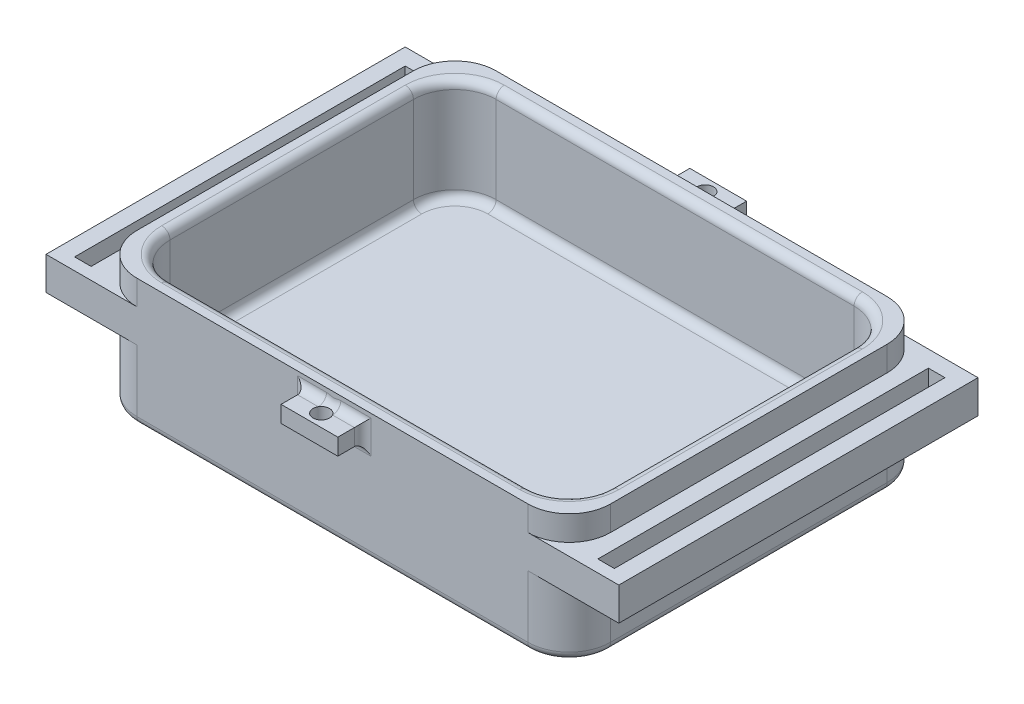
SolidWorks part; units mm, degrees
ref_plane "Front Plane" through (0, 0, 0) normal (0, 0, 1) x (1, 0, 0)
ref_plane "Top Plane" through (0, 0, 0) normal (0, 1, 0) x (1, 0, 0)
ref_plane "Right Plane" through (0, 0, 0) normal (1, 0, 0) x (0, 0, -1)
sketch "Sketch1" plane through (0, 0, 0) normal (0, 1, 0) x (1, 0, 0)
  line L1 (-20.155, 15.23) -> (20.155, 15.23)
  line L2 (-20.155, 15.23) -> (-20.155, -15.23)
  line L3 (-20.155, -15.23) -> (20.155, -15.23)
  line L4 (20.155, 15.23) -> (20.155, -15.23)
  line L5 (-26.155, 4.24) -> (-20.155, 4.24)
  line L6 (-26.155, 4.24) -> (-26.155, -11.5)
  line L7 (-26.155, -11.5) -> (-20.155, -11.5)
  line L8 (-20.155, 4.24) -> (-20.155, -11.5)
  circle A0 centre (17.845, 12.5) radius 1
  circle A1 centre (17.845, -11.5) radius 1
  circle A2 centre (-18.155, -11.5) radius 1
  dimension "D5" = 2
  dimension "D8" = 3.73
  dimension "D10" = 2
  dimension "D11" = 3.73
  dimension "D13" = 2
  dimension "D1" = 40.31
  dimension "D2" = 30.46
  dimension "D3" = 15.23
  dimension "D4" = 20.155
  dimension "D6" = 2.73
  dimension "D7" = 2.31
  dimension "D9" = 2.31
  dimension "D12" = 2
  dimension "D14" = 15.74
  dimension "D15" = 6
  dimension "D16" = 8
  dimension "D17" = 0
sketch "Sketch2" plane through (0, 0, 0) normal (0, 1, 0) x (1, 0, 0)
  line L0 (-20.155, 15.23) -> (20.155, 15.23) construction
  line L1 (-29.655, 18.23) -> (23.655, 18.23)
  line L2 (-29.655, 18.23) -> (-29.655, -21.23)
  line L3 (-29.655, -21.23) -> (23.655, -21.23)
  line L4 (23.655, 18.23) -> (23.655, -21.23)
  line L5 (-20.155, -15.23) -> (20.155, -15.23) construction
  line L6 (20.155, 15.23) -> (20.155, -15.23) construction
  line L7 (-26.155, 4.24) -> (-26.155, -11.5) construction
  line L9 (-31.655, 20.23) -> (25.655, 20.23)
  line L10 (-31.655, 20.23) -> (-31.655, -23.23)
  line L11 (-31.655, -23.23) -> (25.655, -23.23)
  line L12 (25.655, 20.23) -> (25.655, -23.23)
  dimension "D1" = 3
  dimension "D2" = 6
  dimension "D3" = 3.5
  dimension "D4" = 3.5
  dimension "D5" = 2
  dimension "D6" = 2
  dimension "D7" = 2
  dimension "D8" = 2
extrude "Boss-Extrude1" add sketch "Sketch2" along normal blind 5 and the other way blind 7.5
fillet "Fillet1" radius 5 8 edges at (-31.655, -1.25, -20.23) (25.655, -1.25, -20.23) (25.655, -1.25, 23.23) (-31.655, -1.25, 23.23) (23.655, -1.25, 21.23) (-29.655, -1.25, 21.23) (23.655, -1.25, -18.23) (-29.655, -1.25, -18.23)
sketch "Sketch3" plane through (0, -7.5, 0) normal (0, -1, 0) x (1, 0, 0)
  line L4 (-31.655, 18.23) -> (-31.655, -15.23)
  line L5 (-26.655, -20.23) -> (20.655, -20.23)
  line L6 (25.655, -15.23) -> (25.655, 18.23)
  line L7 (20.655, 23.23) -> (-26.655, 23.23)
  line L8 (-31.655, 18.23) -> (-31.655, -15.23)
  line L9 (-26.655, -20.23) -> (20.655, -20.23)
  line L10 (25.655, -15.23) -> (25.655, 18.23)
  line L11 (20.655, 23.23) -> (-26.655, 23.23)
  arc A4 (-31.655, -15.23) -> (-26.655, -20.23) centre (-26.655, -15.23) ccw
  arc A5 (20.655, -20.23) -> (25.655, -15.23) centre (20.655, -15.23) ccw
  arc A6 (25.655, 18.23) -> (20.655, 23.23) centre (20.655, 18.23) ccw
  arc A7 (-26.655, 23.23) -> (-31.655, 18.23) centre (-26.655, 18.23) ccw
  arc A8 (-31.655, -15.23) -> (-26.655, -20.23) centre (-26.655, -15.23) ccw
  arc A9 (20.655, -20.23) -> (25.655, -15.23) centre (20.655, -15.23) ccw
  arc A10 (25.655, 18.23) -> (20.655, 23.23) centre (20.655, 18.23) ccw
  arc A11 (-26.655, 23.23) -> (-31.655, 18.23) centre (-26.655, 18.23) ccw
  dimension "D1" = 0
extrude "Boss-Extrude2" add sketch "Sketch3" along normal blind 3
fillet "Fillet2" radius 1 16 edges at (-28.1905, -7.5, -16.7655) (-3, -7.5, -18.23) (22.1905, -7.5, -16.7655) (23.655, -7.5, 1.5) (22.1905, -7.5, 19.7655) (-3, -7.5, 21.23) (-28.1905, -7.5, 19.7655) (-29.655, -7.5, 1.5) (-28.1905, 5, -16.7655) (-3, 5, -18.23) (22.1905, 5, -16.7655) (23.655, 5, 1.5) (22.1905, 5, 19.7655) (-3, 5, 21.23) (-28.1905, 5, 19.7655) (-29.655, 5, 1.5)
sketch "Sketch6" plane through (0, 0, 0) normal (0, 1, 0) x (1, 0, 0)
  line L0 (-37.655, 20.23) -> (-37.655, -23.23)
  line L1 (20.655, 20.23) -> (31.655, 20.23)
  line L2 (25.655, 15.23) -> (25.655, -18.23)
  line L3 (-31.655, 15.23) -> (-31.655, -18.23) construction
  line L4 (31.655, 20.23) -> (31.655, -23.23)
  line L5 (-31.655, 15.23) -> (-31.655, -18.23)
  line L6 (20.655, -23.23) -> (31.655, -23.23)
  line L7 (27.655, 18.23) -> (29.655, 18.23)
  line L8 (27.655, 18.23) -> (27.655, -21.77)
  line L9 (27.655, -21.77) -> (29.655, -21.77)
  line L10 (29.655, 18.23) -> (29.655, -21.77)
  line L11 (-26.655, 20.23) -> (-37.655, 20.23)
  line L12 (-37.655, -23.23) -> (-26.655, -23.23)
  line L14 (-35.655, 18.23) -> (-33.655, 18.23)
  line L15 (-35.655, 18.23) -> (-35.655, -21.77)
  line L16 (-35.655, -21.77) -> (-33.655, -21.77)
  line L17 (-33.655, 18.23) -> (-33.655, -21.77)
  arc A0 (25.655, 15.23) -> (20.655, 20.23) centre (20.655, 15.23) ccw construction
  arc A1 (20.655, -23.23) -> (25.655, -18.23) centre (20.655, -18.23) ccw construction
  arc A2 (25.655, 15.23) -> (20.655, 20.23) centre (20.655, 15.23) ccw
  arc A3 (20.655, -23.23) -> (25.655, -18.23) centre (20.655, -18.23) ccw
  arc A4 (-26.655, 20.23) -> (-31.655, 15.23) centre (-26.655, 15.23) ccw construction
  arc A5 (-31.655, -18.23) -> (-26.655, -23.23) centre (-26.655, -18.23) ccw construction
  arc A7 (-26.655, 20.23) -> (-31.655, 15.23) centre (-26.655, 15.23) ccw
  arc A8 (-31.655, -18.23) -> (-26.655, -23.23) centre (-26.655, -18.23) ccw
  dimension "D1" = 6
  dimension "D2" = 2
  dimension "D3" = 2
  dimension "D4" = 40
  dimension "D5" = 2
  dimension "D6" = 6
  dimension "D7" = 2
  dimension "D8" = 2
  dimension "D9" = 40
  dimension "D10" = 2
extrude "Boss-Extrude3" add sketch "Sketch6" against normal mid plane 4
fillet "Fillet3" radius 1 8 edges at (24.1905, -10.5, -18.7655) (-3, -10.5, -20.23) (-30.1905, -10.5, -18.7655) (-31.655, -10.5, 1.5) (-30.1905, -10.5, 21.7655) (-3, -10.5, 23.23) (24.1905, -10.5, 21.7655) (25.655, -10.5, 1.5)
sketch "Sketch7" plane through (0, 0, 23.23) normal (0, 0, 1) x (1, 0, 0)
  line L0 (25.655, 5) -> (25.655, 2) construction
  line L1 (-6.2145, 3.5) -> (0.655, 3.5)
  line L2 (-6.2145, 3.5) -> (-6.2145, 1.5)
  line L3 (-6.2145, 1.5) -> (0.655, 1.5)
  line L4 (0.655, 3.5) -> (0.655, 1.5)
  line L5 (-31.655, 2) -> (-31.655, 5) construction
  line L6 (-26.655, 5) -> (20.655, 5) construction
  dimension "D1" = 25.4405
  dimension "D2" = 25
  dimension "D3" = 2
  dimension "D4" = 1.5
sketch "Sketch8" plane through (0, 0, -20.23) normal (0, 0, -1) x (-1, 0, 0)
  line L1 (-0.655, 3.5) -> (6.2145, 3.5)
  line L2 (-0.655, 3.5) -> (-0.655, 1.5)
  line L3 (-0.655, 1.5) -> (6.2145, 1.5)
  line L4 (6.2145, 3.5) -> (6.2145, 1.5)
extrude "Boss-Extrude4" add sketch "Sketch7" along normal blind 3
extrude "Boss-Extrude5" add sketch "Sketch8" along normal blind 3
sketch "Sketch9" plane through (0, 3.5, 0) normal (0, 1, 0) x (1, 0, 0)
  line L0 (0.655, -26.23) -> (0.655, -23.23) construction
  line L1 (-26.655, -23.23) -> (20.655, -23.23) construction
  circle A0 centre (-2.845, -24.73) radius 1
  point P2 (0.655, -24.73)
  dimension "D1" = 3.5
  dimension "D2" = 1.5
sketch "Sketch10" plane through (0, 3.5, 0) normal (0, 1, 0) x (1, 0, 0)
  line L0 (-6.2145, 20.23) -> (0.655, 20.23) construction
  line L1 (0.655, 23.23) -> (0.655, 20.23) construction
  circle A0 centre (-2.845, 21.73) radius 1
  dimension "D1" = 1.5
  dimension "D2" = 3.5
extrude "Cut-Extrude1" cut sketch "Sketch10" against normal blind 3
extrude "Cut-Extrude2" cut sketch "Sketch9" against normal blind 3
fillet "Fillet4" radius 1 8 edges at (-6.2145, 2.5, 23.23) (-2.7798, 1.5, 23.23) (0.655, 2.5, 23.23) (-2.7798, 3.5, 23.23) (-2.7798, 1.5, -20.23) (-6.2145, 2.5, -20.23) (0.655, 2.5, -20.23) (-2.7798, 3.5, -20.23)
